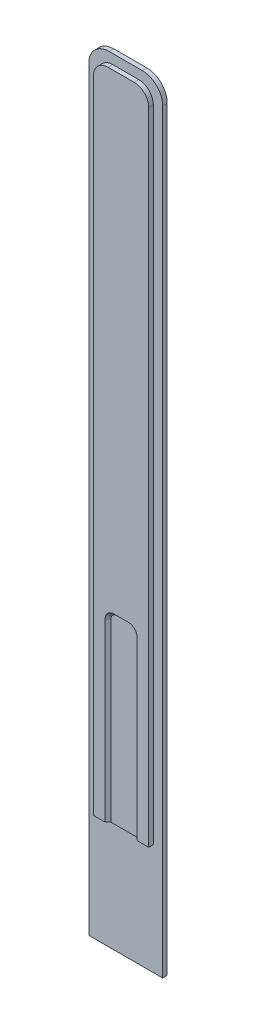
SolidWorks part; units mm, degrees
material "Acrylic (Medium-high impact)"
ref_plane "Front" through (0, 0, 0) normal (0, 0, 1) x (1, 0, 0)
ref_plane "Top" through (0, 0, 0) normal (0, 1, 0) x (1, 0, 0)
ref_plane "Right" through (0, 0, 0) normal (1, 0, 0) x (0, 0, -1)
ref_plane "new front for the battle" through (0, 0, 250.461) normal (0, 0, 1) x (1, 0, 0)
sketch "Sketch1" plane through (0, 0, 250.461) normal (0, 0, 1) x (1, 0, 0)
  line L0 (-76.9, -219) -> (-26.1, -219) construction
  line L1 (-62.9, 238.2) -> (-40.1, 238.2)
  line L2 (-76.9, 224.2) -> (-76.9, -219)
  line L4 (-26.1, 224.2) -> (-26.1, -219)
  line L5 (-76.9, 238.2) -> (-26.1, -219) construction
  line L6 (-76.9, -219) -> (-26.1, 238.2) construction
  line L8 (-76.9, -219) -> (-76.9, -295.2)
  line L9 (-76.9, -295.2) -> (-26.1, -295.2)
  line L10 (-26.1, -219) -> (-26.1, -295.2)
  arc A0 (-40.1, 238.2) -> (-26.1, 224.2) centre (-40.1, 224.2) cw
  arc A1 (-62.9, 238.2) -> (-76.9, 224.2) centre (-62.9, 224.2) ccw
  point P0 (-51.5, 9.6)
  dimension "D5" = 14
  dimension "D1" = 76.2
  dimension "D2" = 457.2
  dimension "D3" = 50.8
  dimension "D4" = 51.5
  dimension "D6" = 219
extrude "Boss-Extrude2" add sketch "Sketch1" along normal mid plane 3.175 separate body
sketch "Sketch2" plane through (0, 0, 250.461) normal (0, 0, 1) x (1, 0, 0)
  line L0 (-40.1, 238.2) -> (-62.9, 238.2) construction
  line L1 (-60.5, 231.6) -> (-42.5, 231.6)
  line L2 (-70.5, 221.6) -> (-70.5, -219)
  line L3 (-70.5, -219) -> (-32.5, -219)
  line L4 (-32.5, 221.6) -> (-32.5, -219)
  line L5 (-76.9, -219) -> (-26.1, -219) construction
  arc A0 (-42.5, 231.6) -> (-32.5, 221.6) centre (-42.5, 221.6) cw
  arc A1 (-60.5, 231.6) -> (-70.5, 221.6) centre (-60.5, 221.6) ccw
  point P4 (-51.5, 231.6)
  point P5 (-51.5, 238.2)
  point P13 (-32.5, 231.6)
  point P16 (-70.5, 231.6)
  dimension "D3" = 10
  dimension "D1" = 6.6
  dimension "D2" = 38
extrude "Boss-Extrude3" add sketch "Sketch2" along normal mid plane 9.525
sketch "Sketch3" plane through (0, 0, 255.2235) normal (0, 0, 1) x (1, 0, 0)
  line L1 (-60.5, -219) -> (-42.5, -219)
  line L2 (-60.5, -219) -> (-60.5, -98)
  line L3 (-56.5, -94) -> (-46.5, -94)
  line L4 (-42.5, -219) -> (-42.5, -98)
  line L5 (-70.5, -219) -> (-32.5, -219) construction
  arc A0 (-46.5, -94) -> (-42.5, -98) centre (-46.5, -98) cw
  arc A1 (-60.5, -98) -> (-56.5, -94) centre (-56.5, -98) cw
  point P6 (-51.5, -219)
  point P10 (-42.5, -94)
  point P13 (-60.5, -94)
  dimension "D3" = 4
  dimension "D1" = 125
  dimension "D2" = 18
extrude "Cut-Extrude1" cut sketch "Sketch3" against normal blind 2
mirror "Mirror2" about plane through (0, 0, 250.461) normal (0, 0, 1) of "Cut-Extrude1"
chamfer "Chamfer1" distance 2 angle 45 10 edges at (-42.5, -158.5, 245.6985) (-60.5, -158.5, 245.6985) (-43.6716, -95.1716, 245.6985) (-59.3284, -95.1716, 245.6985) (-51.5, -94, 245.6985) (-42.5, -158.5, 255.2235) (-60.5, -158.5, 255.2235) (-43.6716, -95.1716, 255.2235) (-59.3284, -95.1716, 255.2235) (-51.5, -94, 255.2235)
